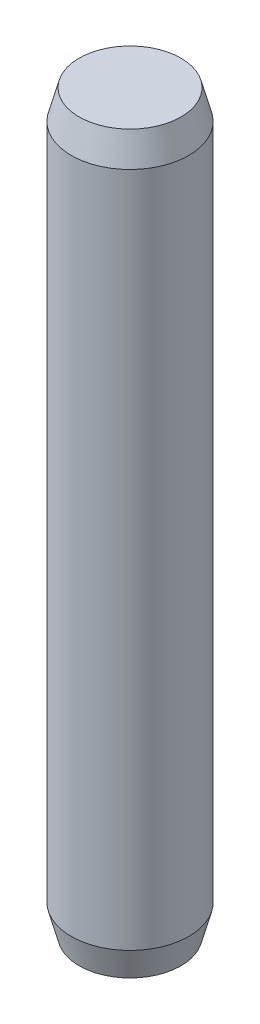
SolidWorks part; units mm, degrees
ref_plane "前视基准面" through (0, 0, 0) normal (0, 0, 1) x (1, 0, 0)
ref_plane "上视基准面" through (0, 0, 0) normal (0, 1, 0) x (1, 0, 0)
ref_plane "右视基准面" through (0, 0, 0) normal (1, 0, 0) x (0, 0, -1)
sketch "草图2" plane through (0, 0, 0) normal (0, 0, 1) x (1, 0, 0)
  line L0 (1.7321, 25) -> (2, 24)
  line L1 (0, 0) -> (1.7321, 0)
  line L2 (0, 0) -> (0, 25)
  line L3 (0, 25) -> (1.7321, 25)
  line L4 (2, 1) -> (2, 24)
  line L5 (2, 1) -> (1.7321, 0)
  dimension "D1" = 2
  dimension "D2" = 25
  dimension "D3" = 1
  dimension "D4" = 15
  dimension "D5" = 1
revolve "旋转1" add sketch "草图2" angle 360 about L2
ref_axis "基准轴1" through (0, 24, 0) along (0, -1, 0)
ref_plane "基准面1" through (0, 12.5, 0) normal (0, 1, 0) x (1, 0, 0)
equation "\"D5@草图2\"=\"D3@草图2\""
